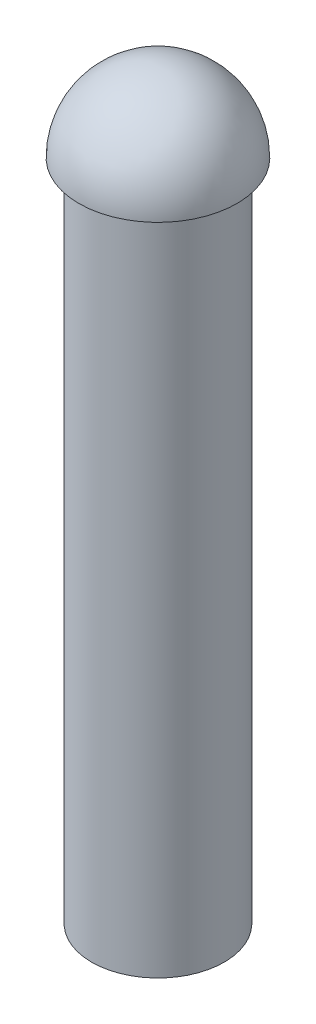
SolidWorks part; units mm, degrees
ref_plane "前视基准面" through (0, 0, 0) normal (0, 0, 1) x (1, 0, 0)
ref_plane "上视基准面" through (0, 0, 0) normal (0, 1, 0) x (1, 0, 0)
ref_plane "右视基准面" through (0, 0, 0) normal (1, 0, 0) x (0, 0, -1)
other "Configuration Table"
sketch "草图1" plane through (0, 0, 0) normal (0, 1, 0) x (1, 0, 0)
  line L0 (0, 7.75) -> (0, -7.75)
  arc A0 (0, -7.75) -> (0, 7.75) centre (0, 0) ccw
  dimension "D1" = 15.5
revolve "旋转1" add sketch "草图1" angle 180 about L0
sketch "草图6" plane through (0, 0, 0) normal (1, 0, 0) x (0, 0, -1)
  line L1 (0, 0) -> (6.5, 0)
  line L2 (0, 0) -> (0, -65)
  line L3 (0, -65) -> (6.5, -65)
  line L4 (6.5, 0) -> (6.5, -65)
  dimension "D1" = 6.5
  dimension "D2" = 65
revolve "旋转2" add sketch "草图6" angle 360 about L2
hole_wizard "M8 螺纹孔1" positions "3D草图1" profile "草图8" tap size "M8" standard "GB"
sketch3d "3D草图1"
  line L0 (0, 0, -7.75) -> (0, 0, 7.75) construction
  circle A0 centre (0, -65, 0) radius 6.5 construction
  point P0 (0, 0, 1.5941)
  point P4 (0, -65, 0)
  point P7 (0, -58.5, 0)
  dimension "D1" = 0
sketch "草图8" plane through (0, -65, 0) normal (1, 0, 0) x (0, 0, -1)
  line L0 (0, 0) -> (0, 32.0429)
  line L1 (0, 32.0429) -> (3.4, 30)
  line L2 (3.4, 30) -> (3.4, 0.625)
  line L3 (3.4, 0.625) -> (4.025, 0)
  line L5 (4.025, 0) -> (0, 0)
  line L6 (-3.4, 0.625) -> (-4.025, 0) construction
  line L10 (0, 32.0429) -> (-3.4, 30) construction
  line L11 (0, -6.35) -> (0, 107.95) construction
  dimension "螺纹孔钻头直径" = 6.8
  dimension "螺纹孔钻头深度" = 30
  dimension "近端锥形沉头孔直径" = 8.05
  dimension "近端锥形沉头孔角度" = 90
  dimension "导头角度" = 118
cosmetic thread "孔螺纹线8" parameters "D1"=30, "D2"=8
thread "螺纹线1" pitch 1.25 start angle 0, offset 0, length 30, pitch 1.25, diameter 6.8
ref_plane "基准面1" through (3.4, -65, 0) normal (0, 0, 1) x (1, 0, 0)
sketch "螺纹线轮廓1" plane through (3.4, -65, 0) normal (0, 0, 1) x (1, 0, 0)
  line L0 (0, 0) -> (0, 1.25) construction
  line L1 (0, 0) -> (0.6766, 0.3906)
  line L2 (0.6766, 0.3906) -> (0.6766, 0.5469)
  line L3 (0.6766, 0.5469) -> (0, 0.9375)
  line L4 (0.6766, 0.4687) -> (0, 0.4687) construction
  line L11 (0, 0) -> (0, 0.9375)
  point P2 (0, 0)
  dimension "Pitch" = 1.25
  dimension "Profile_Angle" = 60
  dimension "Profile_Land" = 0.1562
  dimension "Profile_Height" = 0.6766
